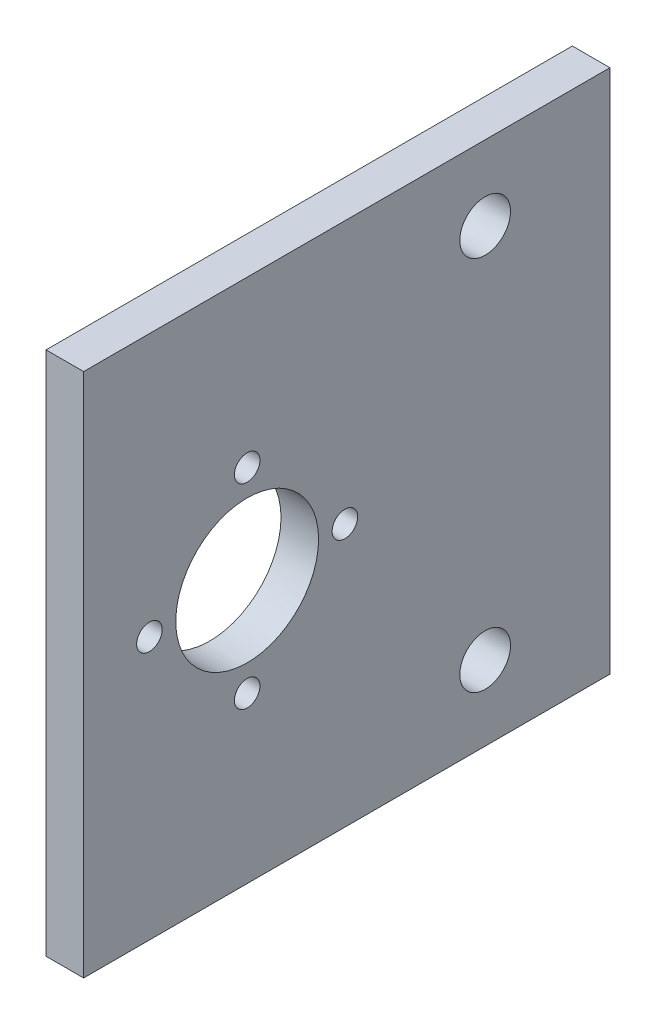
SolidWorks part; units mm, degrees
ref_plane "Front Plane" through (0, 0, 0) normal (1, 0, 0) x (0, 1, 0)
ref_plane "Top Plane" through (0, 0, 0) normal (0, 0, 1) x (0, 1, 0)
ref_plane "Right Plane" through (0, 0, 0) normal (0, 1, 0) x (-1, 0, 0)
sketch "Sketch1" plane through (0, 0, 0) normal (1, 0, 0) x (0, 1, 0)
  line L0 (-34.925, 13.25) -> (34.925, 13.25) construction
  line L1 (-34.925, -35) -> (34.925, -35)
  line L2 (-34.925, -35) -> (-34.925, 35)
  line L3 (-34.925, 35) -> (34.925, 35)
  line L4 (34.925, -35) -> (34.925, 35)
  line L5 (-34.925, -35) -> (34.925, 35) construction
  line L6 (-34.925, 35) -> (34.925, -35) construction
  line L7 (0, 35) -> (0, -35) construction
  line L8 (-34.925, -18.4) -> (34.925, -18.4) construction
  circle A1 centre (0, 26.25) radius 1.7
  circle A2 centre (0, 0.25) radius 1.7
  circle A3 centre (-13, 13.25) radius 1.7
  circle A4 centre (13, 13.25) radius 1.7
  circle A5 centre (0, 13.25) radius 9.5
  circle A6 centre (-25, -18.4) radius 3.3731
  circle A7 centre (25, -18.4) radius 3.3731
  point P0 (0, 0)
  dimension "D5" = 13
  dimension "D4" = 3.4
  dimension "D8" = 19
  dimension "D10" = 6.7462
  dimension "D1" = 70
  dimension "D2" = 69.85
  dimension "D3" = 48.25
  dimension "D7" = 13
  dimension "D9" = 16.6
  dimension "D11" = 25
extrude "Boss-Extrude1" add sketch "Sketch1" along normal blind 5
